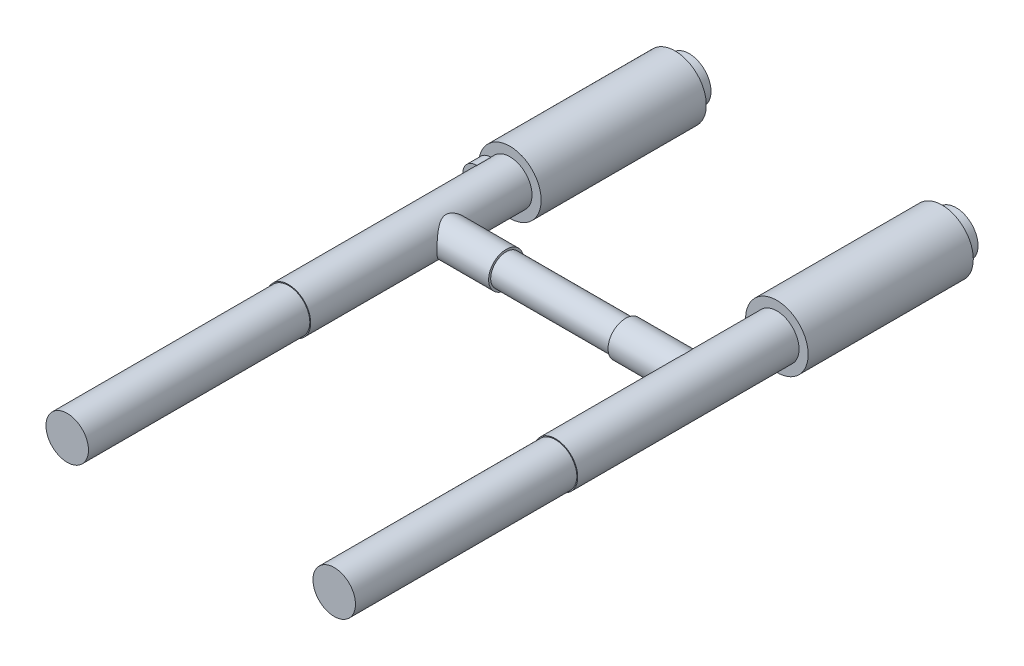
SolidWorks part; units mm, degrees
ref_plane "Front Plane" through (0, 0, 0) normal (0, 0, 1) x (1, 0, 0)
ref_plane "Top Plane" through (0, 0, 0) normal (0, 1, 0) x (1, 0, 0)
ref_plane "Right Plane" through (0, 0, 0) normal (1, 0, 0) x (0, 0, -1)
sketch "Sketch1" plane through (0, 0, 0) normal (0, 0, 1) x (1, 0, 0)
  circle A0 centre (0, 0) radius 7.9375
  dimension "D1" = 15.875
extrude "Boss-Extrude1" add sketch "Sketch1" along normal blind 5.08
sketch "Sketch2" plane through (0, 0, 5.08) normal (0, 0, 1) x (1, 0, 0)
  circle A0 centre (0, 0) radius 11.303
extrude "Boss-Extrude2" add sketch "Sketch2" along normal blind 59.69
sketch "Sketch3" plane through (0, 0, 64.77) normal (0, 0, 1) x (1, 0, 0)
  circle A0 centre (0, 0) radius 8.001
extrude "Boss-Extrude3" add sketch "Sketch3" along normal blind 80.01
sketch "Sketch4" plane through (0, 0, 144.78) normal (0, 0, 1) x (1, 0, 0)
  circle A0 centre (0, 0) radius 7.6835
extrude "Boss-Extrude4" add sketch "Sketch4" along normal blind 80.01
ref_axis "Axis1" through (0, 0, 254.54) along (0, 0, -1)
sketch "Sketch5" plane through (0, 0, 64.77) normal (0, 0, 1) x (1, 0, 0)
  line L0 (0, 0) -> (0, 45.5714) construction
ref_plane "Plane1" through (0, 0, 0) normal (1, 0, 0) x (0, 0, -1)
sketch "Sketch6" plane through (0, 0, 0) normal (1, 0, 0) x (0, 0, -1)
  line L0 (-64.77, 0) -> (-66.7212, 0) construction
  line L1 (-64.77, 8.001) -> (-64.77, -8.001) construction
  line L3 (-66.7212, 6.35) -> (-71.8012, 6.35)
  line L4 (-66.7212, 6.35) -> (-66.7212, -6.35)
  line L5 (-66.7212, -6.35) -> (-71.8012, -6.35)
  line L6 (-71.8012, 6.35) -> (-71.8012, -6.35)
  dimension "D1" = 12.7
  dimension "D2" = 5.08
extrude "Boss-Extrude5" add sketch "Sketch6" against normal blind 10.01
fillet "Fillet1" radius 5 2 edges at (-10.01, -6.35, 69.2612) (-10.01, 6.35, 69.2612)
sketch "Sketch7" plane through (0, 0, 0) normal (1, 0, 0) x (0, 0, -1)
  line L0 (-64.77, 0) -> (-86.4387, 0) construction
  line L1 (-64.77, 8.001) -> (-64.77, -8.001) construction
  line L2 (-86.4387, 0) -> (-92.7887, 0) construction
  circle A0 centre (-92.7887, 0) radius 6.35
extrude "Boss-Extrude6" add sketch "Sketch7" along normal blind 26.67
sketch "Sketch8" plane through (26.67, 0, 0) normal (1, 0, 0) x (0, 0, -1)
  circle A0 centre (-92.7887, 0) radius 5.588
extrude "Boss-Extrude7" add sketch "Sketch8" along normal blind 21.59
ref_plane "Plane2" through (48.26, 0, 0) normal (1, 0, 0) x (0, 0, -1)
mirror "Mirror2" about plane through (48.26, 0, 92.7887) normal (1, 0, 0) of "Boss-Extrude7", "Boss-Extrude6", "Boss-Extrude1", "Boss-Extrude2", "Boss-Extrude3", "Boss-Extrude4"
